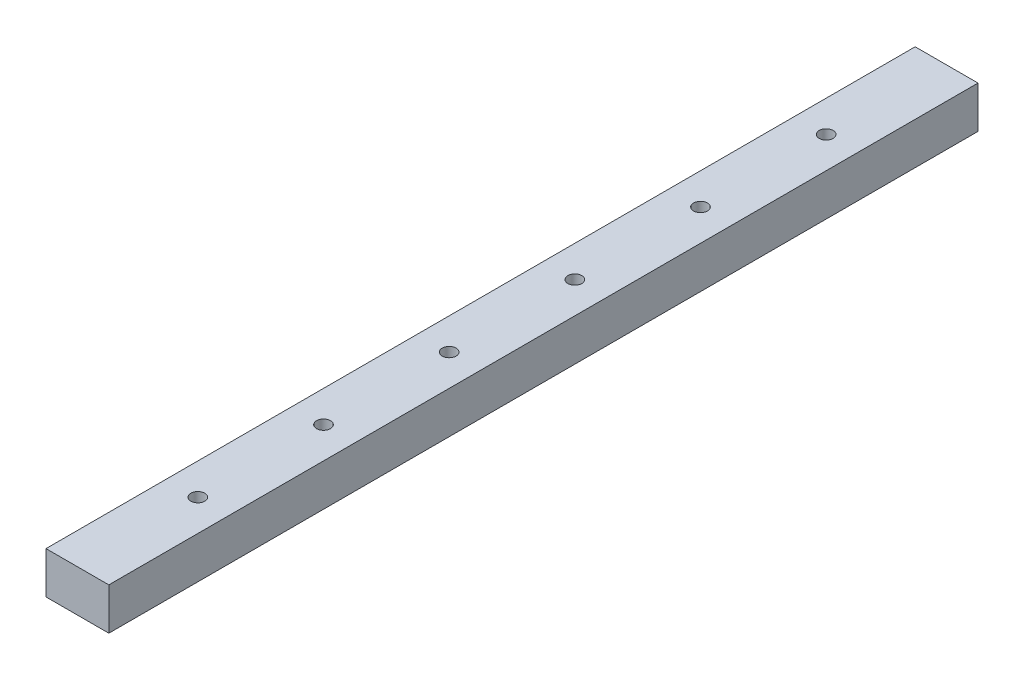
SolidWorks part; units mm, degrees
ref_plane "Front Plane" through (0, 0, 0) normal (0, 0, 1) x (1, 0, 0)
ref_plane "Top Plane" through (0, 0, 0) normal (0, 1, 0) x (1, 0, 0)
ref_plane "Right Plane" through (0, 0, 0) normal (1, 0, 0) x (0, 0, -1)
sketch "Sketch1" plane through (0, 0, 0) normal (0, 0, 1) x (1, 0, 0)
  line L1 (22.225, -12.7) -> (-22.225, -12.7)
  line L2 (22.225, -12.7) -> (22.225, 12.7)
  line L3 (22.225, 12.7) -> (-22.225, 12.7)
  line L4 (-22.225, -12.7) -> (-22.225, 12.7)
  line L5 (22.225, -12.7) -> (-22.225, 12.7) construction
  line L6 (22.225, 12.7) -> (-22.225, -12.7) construction
  line L7 (22.225, 12.7) -> (15.875, 12.7)
  line L8 (22.225, 12.7) -> (22.225, -12.7)
  line L9 (22.225, -12.7) -> (15.875, -12.7)
  line L10 (15.875, 12.7) -> (15.875, -12.7)
  point P0 (0, 0)
  dimension "D1" = 25.4
  dimension "D2" = 44.45
  dimension "D3" = 6.35
  dimension "D4" = 25.4
extrude "Boss-Extrude1" add sketch "Sketch1" along normal blind 527.05 contours L10 L3 L4 L1 L2 L9 region at (-3.175, 0, 0)
hole_wizard "CSK for 5/16 Flat Head Machine Screw1" positions "Sketch2" profile "Sketch3" countersink size "5/16" standard "ANSI Inch" end condition through all
sketch "Sketch2" plane through (0, -12.7, 0) normal (0, -1, 0) x (-1, 0, 0)
  line L0 (-15.875, -527.05) -> (22.225, -527.05) construction
  line L1 (22.225, -527.05) -> (22.225, 0) construction
  line L2 (-15.875, 0) -> (22.225, 0) construction
  point P0 (3.175, -454.025)
  point P15 (3.175, -377.825)
  point P16 (3.175, -301.625)
  point P17 (3.175, -225.425)
  point P18 (3.175, -149.225)
  point P19 (3.175, -73.025)
  dimension "D1" = 73.025
  dimension "D2" = 19.05
  dimension "D4" = 73.025
  dimension "D3" = 6
sketch "Sketch3" plane through (-3.175, -12.7, 454.025) normal (1, 0, 0) x (0, 0, -1)
  line L0 (0, 0) -> (0, 25.4)
  line L1 (0, 25.4) -> (4.2164, 25.4)
  line L2 (4.2164, 25.4) -> (4.2164, 4.4267)
  line L3 (4.2164, 4.4267) -> (8.0645, 0)
  line L5 (8.0645, 0) -> (0, 0)
  line L6 (-4.2164, 4.4267) -> (-8.0645, 0) construction
  line L11 (0, -6.35) -> (0, 107.95) construction
  dimension "Thru Hole Dia." = 8.4328
  dimension "Thru Hole Depth" = 25.4
  dimension "Near C'Sink Dia." = 16.129
  dimension "Near C'Sink Angle" = 82
